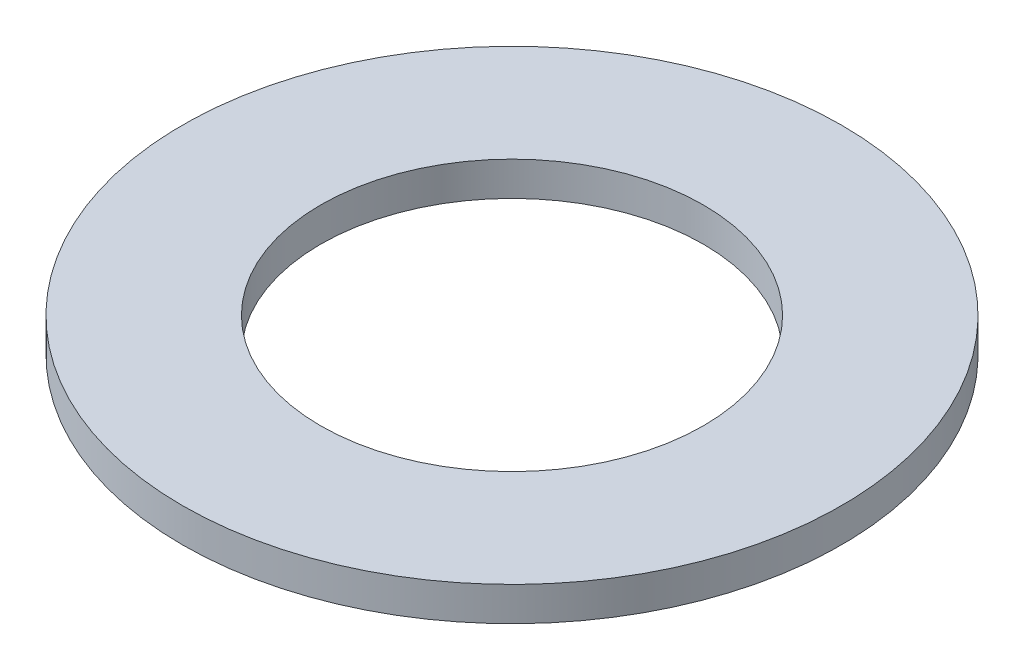
SolidWorks part; units mm, degrees
ref_plane "Front Plane" through (0, 0, 0) normal (0, 0, 1) x (1, 0, 0)
ref_plane "Top Plane" through (0, 0, 0) normal (0, 1, 0) x (1, 0, 0)
ref_plane "Right Plane" through (0, 0, 0) normal (1, 0, 0) x (0, 0, -1)
sketch "Sketch1" plane through (0, 0, 0) normal (0, 1, 0) x (1, 0, 0)
  circle A0 centre (0, 0) radius 77.5
  dimension "FLANGE_OD" = 155
extrude "Boss-Extrude1" add sketch "Sketch1" along normal blind 8
sketch "Sketch2" plane through (0, 0, 0) normal (0, 1, 0) x (1, 0, 0)
  circle A0 centre (0, 0) radius 45
  dimension "BORE_D" = 90
extrude "Cut-Extrude1" cut sketch "Sketch2" along normal through all
sketch "Sketch3" plane through (0, 8, 0) normal (0, 1, 0) x (1, 0, 0)
  circle A0 centre (0, 0) radius 29.2647 construction
  circle A1 centre (-29.2647, 0) radius 2.6822
  dimension "BOLT_D" = 5.3643
  dimension "BOLT_PCD" = 58.5293
extrude "Cut-Extrude2" cut sketch "Sketch3" against normal blind 6.3316 rebuild error yes
pattern_circular "CirPattern1" count 4 over 360 rebuild error yes
